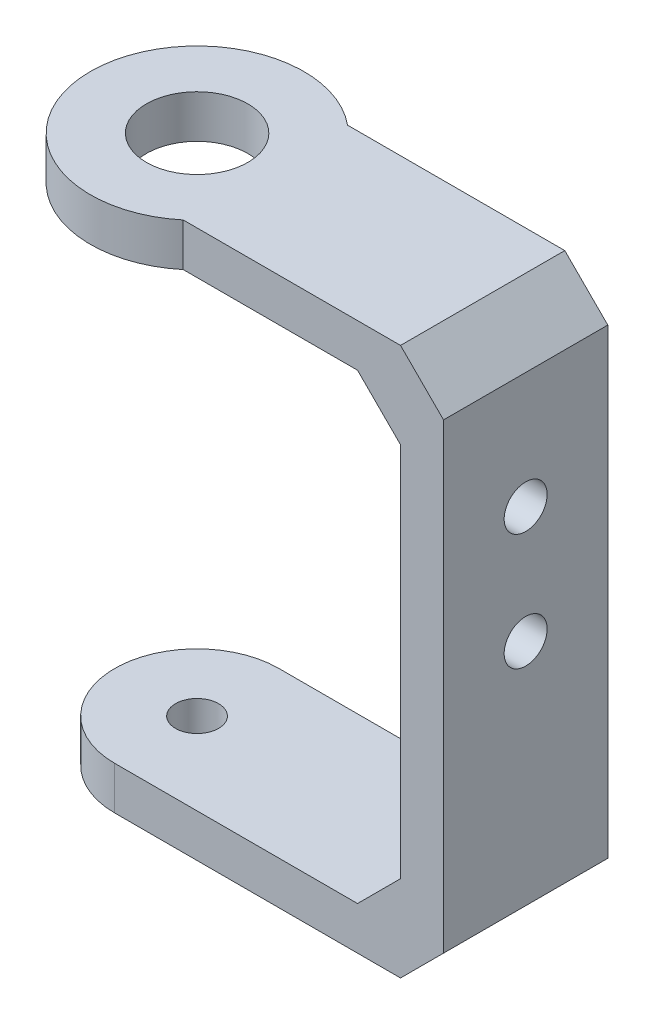
SolidWorks part; units mm, degrees
ref_plane "Front Plane" through (0, 0, 0) normal (0, 0, 1) x (1, 0, 0)
ref_plane "Top Plane" through (0, 0, 0) normal (0, 1, 0) x (1, 0, 0)
ref_plane "Right Plane" through (0, 0, 0) normal (1, 0, 0) x (0, 0, -1)
sketch "Sketch1" plane through (0, 0, 0) normal (0, 0, 1) x (1, 0, 0)
  line L0 (23.7361, 38.9968) -> (26.7361, 35.9968)
  line L1 (26.7361, 35.9968) -> (26.7361, 3.7768)
  line L2 (26.7361, 3.7768) -> (23.7361, 0.7768)
  line L3 (23.7361, 0.7768) -> (20.7361, 3.7768)
  line L4 (20.7361, 3.7768) -> (23.7361, 6.7768)
  line L7 (23.7361, 6.7768) -> (23.7361, 32.9968)
  line L8 (23.7361, 32.9968) -> (20.7361, 35.9968)
  line L9 (20.7361, 35.9968) -> (23.7361, 38.9968)
extrude "Boss-Extrude1" add sketch "Sketch1" along normal blind 5.73 and the other way blind 5.73
sketch "Sketch6" plane through (0, 0, 5.73) normal (0, 0, 1) x (1, 0, 0)
  line L0 (20.7361, 3.7768) -> (8.5761, 3.7768)
  line L1 (23.7361, 0.7768) -> (20.7361, 0.7768)
  line L3 (8.5761, 3.7768) -> (8.5761, 0.7768)
  line L4 (8.5761, 0.7768) -> (20.7361, 0.7768)
  line L5 (23.7361, 0.7768) -> (20.7361, 3.7768)
extrude "Boss-Extrude5" add sketch "Sketch6" against normal blind 11.46 contours L1 L4 L3 L0 L5
sketch "Sketch8" plane through (0, 0, 5.73) normal (0, 0, 1) x (1, 0, 0)
  line L1 (20.7361, 38.9968) -> (23.7361, 38.9968)
  line L2 (20.7361, 38.9968) -> (8.5761, 38.9968)
  line L3 (8.5761, 38.9968) -> (8.5761, 35.9968)
  line L4 (8.5761, 35.9968) -> (20.7361, 35.9968)
  line L5 (23.7361, 38.9968) -> (20.7361, 35.9968)
extrude "Boss-Extrude8" add sketch "Sketch8" against normal blind 11.46
sketch "Sketch9" plane through (0, 38.9968, 0) normal (0, 1, 0) x (1, 0, 0)
  line L0 (8.5761, 5.73) -> (8.5761, -5.73)
  arc A0 (8.5761, 5.73) -> (8.5761, -5.73) centre (3.8148, 0) ccw
extrude "Boss-Extrude9" add sketch "Sketch9" against normal blind 3
sketch "Sketch11" plane through (0, 38.9968, 0) normal (0, 1, 0) x (1, 0, 0)
  circle A1 centre (3.8148, 0) radius 3.54
extrude "Cut-Extrude1" cut sketch "Sketch11" against normal blind 3
sketch "Sketch12" plane through (0, 0.7768, 0) normal (0, -1, 0) x (-1, 0, 0)
  line L0 (-8.5761, 5.73) -> (-3.7931, 5.73)
  line L2 (-3.7931, -5.73) -> (-8.5761, -5.73)
  line L3 (-8.5761, -5.73) -> (-8.5761, 5.73)
  arc A0 (-3.7931, -5.73) -> (-3.7931, 5.73) centre (-3.7931, 0) ccw
extrude "Boss-Extrude10" add sketch "Sketch12" against normal blind 3
sketch "Sketch13" plane through (0, 3.7768, 0) normal (0, 1, 0) x (1, 0, 0)
  circle A0 centre (3.81, 0) radius 1.5
extrude "Cut-Extrude2" cut sketch "Sketch13" against normal blind 3
sketch "Sketch15" plane through (26.7361, 0, 0) normal (1, 0, 0) x (0, 0, -1)
  circle A0 centre (0, 27.8868) radius 1.5
  circle A1 centre (0, 19.7568) radius 1.5
extrude "Cut-Extrude3" cut sketch "Sketch15" against normal up to vertex (3 mm away) up to point (23.7361, 6.7768, 5.73)
